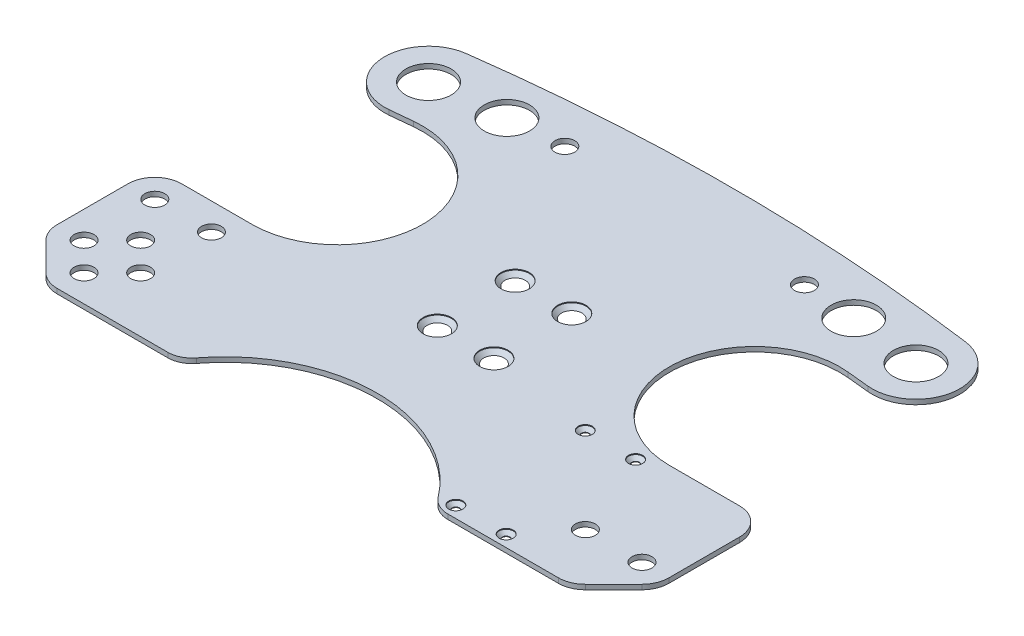
SolidWorks part; units mm, degrees
ref_plane "Front Plane" through (0, 0, 0) normal (0, 0, 1) x (1, 0, 0)
ref_plane "Top Plane" through (0, 0, 0) normal (0, 1, 0) x (1, 0, 0)
ref_plane "Right Plane" through (0, 0, 0) normal (1, 0, 0) x (0, 0, -1)
sketch "Sketch1" plane through (0, 0, 0) normal (0, 1, 0) x (1, 0, 0)
  line L1 (-120, -95) -> (120, -95)
  line L2 (-120, -95) -> (-120, 95)
  line L3 (-120, 95) -> (120, 95)
  line L4 (120, -95) -> (120, 95)
  line L5 (-120, -95) -> (120, 95) construction
  line L6 (-120, 95) -> (120, -95) construction
  line L7 (-10, 13.75) -> (10, 13.75)
  line L8 (-10, 13.75) -> (-10, -13.75)
  line L9 (-10, -13.75) -> (10, -13.75)
  line L10 (10, 13.75) -> (10, -13.75)
  line L11 (-10, 13.75) -> (10, -13.75) construction
  line L12 (-10, -13.75) -> (10, 13.75) construction
  circle A0 centre (0, 0) radius 95
  circle A1 centre (-10, 13.75) radius 2.5
  circle A2 centre (10, 13.75) radius 2.5
  circle A3 centre (10, -13.75) radius 2.5
  circle A4 centre (-10, -13.75) radius 2.5
  circle A5 centre (0, 0) radius 120
  dimension "D3" = 5
  dimension "D1" = 240
  dimension "D2" = 190
  dimension "D4" = 27.5
  dimension "D5" = 20
extrude "Boss-Extrude1" add sketch "Sketch1" along normal blind 1.7 contours A0 A4 L8 A1 L7 A2 L10 A3 L9 | A4 L9 A3 L10 A2 L7 A1 L8 | L3 A5 L1 A0 | L1 A5 L3 A0 region at (-105.6812, 0, 51.9346) region at (68.7642, 0, 68.7642) region at (-92.313, 0, 0) region at (0, 0, 0)
sketch "Sketch2" plane through (0, 1.7, 0) normal (0, 1, 0) x (1, 0, 0)
  line L0 (-81.1673, -40) -> (21.9115, -40) construction
  line L1 (-127.3056, -60) -> (138.909, -60) construction
  line L2 (-88.5406, 28.139) -> (-88.5406, -89.0376) construction
  line L3 (-88.5406, -40) -> (-88.5406, -60) construction
  line L4 (0, 21.6044) -> (0, -21.4213) construction
  line L5 (88.5406, 33.139) -> (88.5406, -84.0376) construction
  line L6 (-151.9803, -25) -> (55.006, -25) construction
  line L7 (-48.8837, 35) -> (62.426, 35) construction
  circle A0 centre (0, 0) radius 35
  circle A1 centre (0, 35) radius 2.5
  circle A2 centre (30.3109, 17.5) radius 2.5
  circle A3 centre (30.3109, -17.5) radius 2.5
  circle A4 centre (0, -35) radius 2.5
  circle A5 centre (-30.3109, -17.5) radius 2.5
  circle A6 centre (-30.3109, 17.5) radius 2.5
  circle A7 centre (-88.5406, -40) radius 3.5
  circle A8 centre (-88.5406, -50) radius 10
  circle A9 centre (-78.5406, -50) radius 3.5
  circle A10 centre (-88.5406, -60) radius 3.5
  circle A11 centre (-98.5406, -50) radius 3.5
  circle A12 centre (78.5406, -50) radius 3.5
  circle A13 centre (98.5406, -50) radius 3.5
  circle A14 centre (-98.5406, -25) radius 3.5
  circle A15 centre (-78.5406, -25) radius 3.5
  circle A16 centre (0, 0) radius 45
  circle A17 centre (0, -580) radius 625
  circle A18 centre (0, -580) radius 645
  circle A19 centre (-86.0945, 59.2282) radius 8
  circle A20 centre (-61.2596, 62.0843) radius 8
  circle A21 centre (-86.0945, 59.2282) radius 15.5
  arc A22 (-73.3144, 95) -> (-73.3144, -95) centre (0, 0) ccw construction
  circle A23 centre (-61.2596, 62.0843) radius 9.5
  circle A24 centre (-86.0945, 59.2282) radius 9.5
  circle A25 centre (61.2596, 62.0843) radius 8
  circle A26 centre (86.0945, 59.2282) radius 8
  circle A27 centre (-42.3209, 63.6101) radius 3.5
  circle A28 centre (0, 0) radius 70
  circle A29 centre (42.3209, 63.6101) radius 3.5
  circle A30 centre (-98.5406, -50) radius 9.5
  circle A31 centre (42.3209, 63.6101) radius 9.5
  circle A32 centre (61.2596, 62.0843) radius 9.5
  point P17 (0, 0)
  point P21 (-88.5406, -50)
  point P37 (-88.5406, -50)
  point P56 (0, 65)
  point P57 (0, 45)
  point P68 (-76.6704, 60.4269)
  point P69 (-70.7097, 61.1124)
  point P81 (0, 0)
  dimension "D1" = 70
  dimension "D2" = 5
  dimension "D4" = 7
  dimension "D9" = 90
  dimension "D10" = 1250
  dimension "D11" = 20
  dimension "D12" = 16
  dimension "D14" = 6
  dimension "D13" = 19
  dimension "D17" = 140
  dimension "D18" = 6
  dimension "D5" = 20
  dimension "D6" = 40
  dimension "D8" = 15
  dimension "D15" = 6
  dimension "D3" = 6
  dimension "D7" = 4
extrude "Cut-Extrude1" cut sketch "Sketch2" against normal up to next contours A7 | A9 | A10 | A11 | A12 | A13 | A14 | A15 | A19 | A20 | A25 | A26 | A27 | A29
sketch "Sketch3" plane through (0, 1.7, 0) normal (0, 1, 0) x (1, 0, 0)
  line L1 (-84.5506, 43.8053) -> (-40.7771, 48.1872)
  line L2 (0, 100.6986) -> (0, -98.8678) construction
  line L3 (-10.3445, 0) -> (20.4144, 0) construction
  line L5 (84.5506, 43.8053) -> (40.7771, 48.1872)
  line L6 (-42.3209, 63.6101) -> (0, 0) construction
  line L7 (-36.306, 26.5871) -> (-55.2257, 55.0243)
  line L8 (-10.4964, 43.7587) -> (-29.4161, 72.1959)
  line L9 (10.4964, 43.7587) -> (29.4161, 72.1959)
  line L10 (36.306, 26.5871) -> (55.2257, 55.0243)
  line L11 (-108.0406, -50) -> (-108.0406, -25)
  line L12 (-98.5406, -15.5) -> (-78.5406, -15.5)
  line L13 (-73.3144, -95) -> (73.3144, -95)
  line L14 (73.3144, 95) -> (-73.3144, 95)
  line L15 (-73.3144, -95) -> (73.3144, -95)
  line L16 (73.3144, 95) -> (-73.3144, 95)
  line L17 (-69.0406, -25) -> (-69.0406, -50)
  line L18 (-71.8231, -56.7175) -> (-81.8231, -66.7175)
  line L19 (-105.2581, -56.7175) -> (-95.2581, -66.7175)
  line L20 (-42.3209, 79.1101) -> (42.3209, 79.1101)
  line L21 (-78.5406, -15.5) -> (-42.2463, -15.5)
  line L22 (0, -45) -> (111.243, -45) construction
  line L23 (-88.5406, -69.5) -> (88.5406, -69.5)
  line L24 (69.0406, -15.5) -> (45.0406, -15.5)
  line L25 (78.5406, -15.5) -> (42.2463, -15.5)
  line L26 (98.5406, -15.5) -> (78.5406, -15.5)
  line L27 (108.0406, -50) -> (108.0406, -25)
  line L28 (105.2581, -56.7175) -> (95.2581, -66.7175)
  line L29 (69.0406, -15.5) -> (69.0406, -69.5)
  line L30 (69.0406, -69.5) -> (45.0406, -69.5)
  line L31 (45.0406, -15.5) -> (45.0406, -69.5)
  line L32 (57.0406, -15.5) -> (57.0406, -69.5) construction
  line L33 (45.0406, -42.5) -> (69.0406, -42.5) construction
  circle A0 centre (-86.0945, 59.2282) radius 15.5
  arc A1 (-73.3144, 95) -> (-73.3144, -95) centre (0, 0) ccw construction
  circle A2 centre (-42.3209, 63.6101) radius 15.5
  circle A3 centre (86.0945, 59.2282) radius 15.5
  circle A4 centre (42.3209, 63.6101) radius 15.5
  circle A5 centre (0, 0) radius 45
  circle A6 centre (-98.5406, -25) radius 9.5
  circle A7 centre (-98.5406, -25) radius 3.5 construction
  arc A8 (-73.3144, 95) -> (-73.3144, -95) centre (0, 0) ccw
  arc A9 (73.3144, -95) -> (73.3144, 95) centre (0, 0) ccw
  arc A10 (-73.3144, 95) -> (-73.3144, -95) centre (0, 0) ccw
  arc A11 (73.3144, -95) -> (73.3144, 95) centre (0, 0) ccw
  circle A12 centre (-78.5406, -25) radius 9.5
  circle A13 centre (-88.5406, -60) radius 9.5
  circle A14 centre (-98.5406, -50) radius 9.5
  circle A15 centre (-78.5406, -50) radius 9.5
  circle A17 centre (98.5406, -50) radius 9.5
  circle A18 centre (78.5406, -50) radius 9.5
  arc A19 (73.3144, -95) -> (73.3144, 95) centre (0, 0) ccw construction
  arc A20 (-45.0406, -69.5) -> (45.0406, -69.5) centre (0, -98.6511) cw
  circle A21 centre (98.5406, -25) radius 9.5
  circle A22 centre (98.5406, -50) radius 9.5
  circle A23 centre (88.5406, -60) radius 9.5
  circle A24 centre (-73.6846, 14.6212) radius 30.1212
  circle A25 centre (73.6846, 14.6212) radius 30.1212
  circle A26 centre (48.1506, -19.64) radius 1.3
  circle A27 centre (65.9306, -19.64) radius 1.3
  circle A28 centre (65.9306, -65.36) radius 1.3
  circle A29 centre (48.1506, -65.36) radius 1.3
  circle A30 centre (0, -580) radius 645
  circle A31 centre (0, -580) radius 660.5
  arc M45 (-73.3144, 95) -> (-73.3144, -95) centre (0, 0) ccw
  line M46 (-73.3144, -95) -> (73.3144, -95)
  arc M47 (73.3144, -95) -> (73.3144, 95) centre (0, 0) ccw
  line M48 (73.3144, 95) -> (-73.3144, 95)
  dimension "D1" = 90
  dimension "D3" = 6
  dimension "D5" = 2.6
  dimension "D4" = 24
  dimension "D6" = 17.78
  dimension "D7" = 45.72
  dimension "D2" = 0
extrude "Cut-Extrude2" cut sketch "Sketch3" against normal up to next contours A24 L1 A0 A14 L11 A6 L12 L21 M45 | A24 | L28 A23 L23 A13 L19 A14 A10 A17 M46 M47 | A20 L23 | L5 A25 L24 L25 L26 A21 L27 A17 A11 A3 | A25 | A30 A0 M45 | A31 A11 M48 M45 | A0 A31 A10 | A31 A3 M47 | A30 A3 M47 | A26 | A27 | A28 | A29 region at (-107.3028, 1.7, -8.797) region at (-73.6846, 1.7, -14.6212) region at (-102.839, 1.7, -59.5932) region at (-94.2652, 1.7, -72.7135) region at (0, 1.7, -86.2332) region at (0, 1.7, 81.3426) region at (0, 1.7, 59.4787) region at (102.839, 1.7, -59.5932) region at (107.3028, 1.7, -8.797) region at (94.2652, 1.7, -72.7135) region at (73.6846, 1.7, -14.6212)
fillet "Fillet1" radius 8.5 2 edges at (-45.0406, 0.85, 69.5) (45.0406, 0.85, 69.5)
hole_wizard "CSK for M5 Flat Head Machine Screw1" positions "Sketch4" profile "Sketch5" countersink size "M5" standard "ANSI Metric"
sketch "Sketch4" plane through (0, 1.7, 0) normal (0, 1, 0) x (1, 0, 0)
  point P0 (-10, 13.75)
  point P3 (10, 13.75)
  point P6 (10, -13.75)
  point P9 (-10, -13.75)
sketch "Sketch5" plane through (-10, 1.7, -13.75) normal (1, 0, 0) x (0, 0, 1)
  line L0 (0, 0) -> (0, 6.5022)
  line L1 (0, 6.5022) -> (2.5, 5)
  line L2 (2.5, 5) -> (2.5, 2.8)
  line L3 (2.5, 2.8) -> (5, 0.3)
  line L4 (5, 0.3) -> (5, 0)
  line L6 (5, 0) -> (0, 0)
  line L7 (-2.5, 2.8) -> (-5, 0.3) construction
  line L10 (0, 6.5022) -> (-2.5, 5) construction
  line L11 (0, -6.35) -> (0, 107.95) construction
  dimension "Hole Dia." = 5
  dimension "Hole Depth" = 5
  dimension "C'Sink Dia." = 10
  dimension "C'Sink Angle" = 90
  dimension "Drill Angle" = 118
  dimension "Head Clearance" = 0.3
hole_wizard "CSK for M2.5 Flat Head Machine Screw1" positions "Sketch6" profile "Sketch7" countersink size "M2.5" standard "ANSI Metric"
sketch "Sketch6" plane through (0, 1.7, 0) normal (0, 1, 0) x (1, 0, 0)
  point P0 (48.1506, -19.64)
  point P3 (65.9306, -19.64)
  point P6 (65.9306, -65.36)
  point P9 (48.1506, -65.36)
sketch "Sketch7" plane through (48.1506, 1.7, 19.64) normal (1, 0, 0) x (0, 0, 1)
  line L0 (0, 0) -> (0, 5.7511)
  line L1 (0, 5.7511) -> (1.25, 5)
  line L2 (1.25, 5) -> (1.25, 1.55)
  line L3 (1.25, 1.55) -> (2.5, 0.3)
  line L4 (2.5, 0.3) -> (2.5, 0)
  line L6 (2.5, 0) -> (0, 0)
  line L7 (-1.25, 1.55) -> (-2.5, 0.3) construction
  line L10 (0, 5.7511) -> (-1.25, 5) construction
  line L11 (0, -6.35) -> (0, 107.95) construction
  dimension "Hole Dia." = 2.5
  dimension "Hole Depth" = 5
  dimension "C'Sink Dia." = 5
  dimension "C'Sink Angle" = 90
  dimension "Drill Angle" = 118
  dimension "Head Clearance" = 0.3
